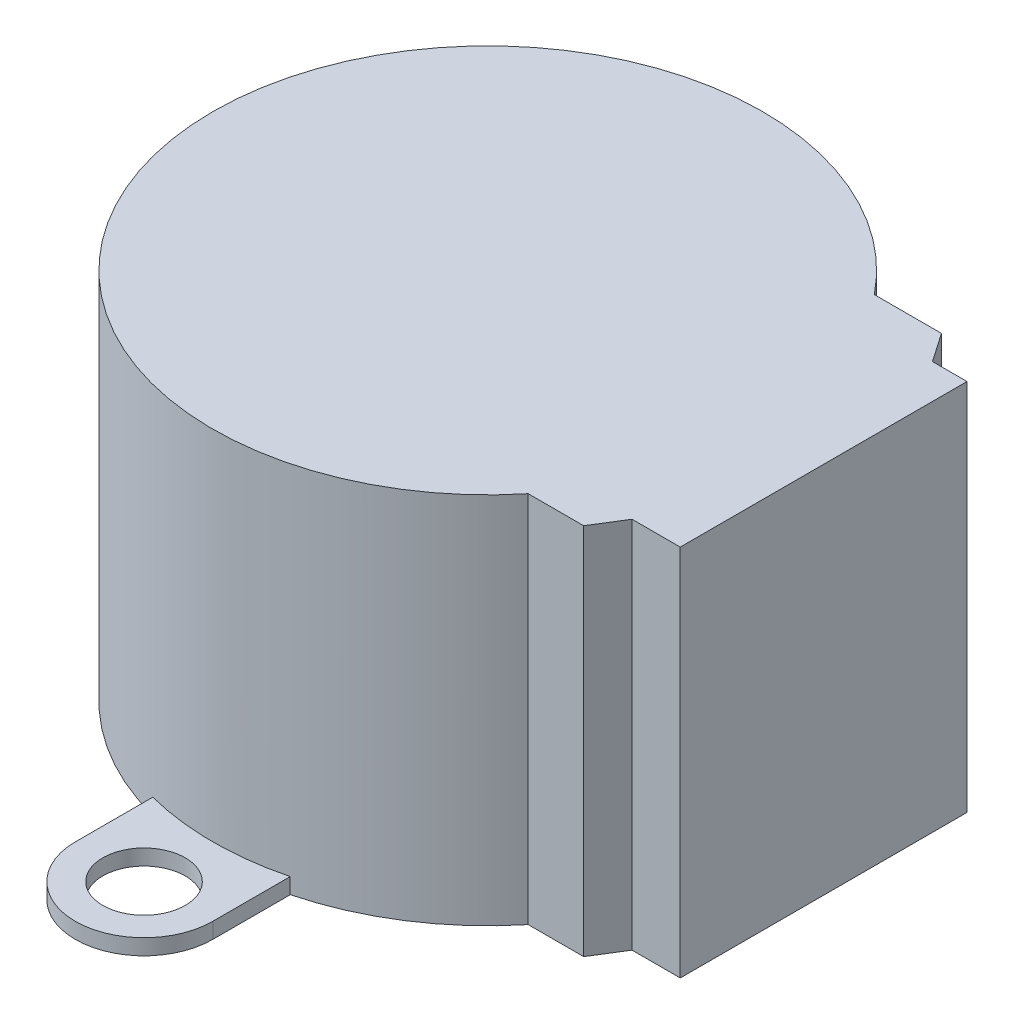
SolidWorks part; units mm, degrees
ref_plane "Front Plane" through (0, 0, 0) normal (0, 0, 1) x (1, 0, 0)
ref_plane "Top Plane" through (0, 0, 0) normal (0, 1, 0) x (1, 0, 0)
ref_plane "Right Plane" through (0, 0, 0) normal (1, 0, 0) x (0, 0, -1)
sketch "Sketch1" plane through (0, 0, 0) normal (0, 1, 0) x (1, 0, 0)
  line L0 (14.3268, 8.7713) -> (15.3419, 7.3)
  line L1 (0, 17.5) -> (0, -17.5) construction
  line L2 (-3.5, 17.5) -> (-3.5, 13.5554)
  line L3 (3.5, 17.5) -> (3.5, 13.5554)
  line L4 (17.1, 7.3) -> (17.1, -7.3)
  line L5 (-3.5, -17.5) -> (-3.5, -13.5554)
  line L6 (3.5, -17.5) -> (3.5, -13.5554)
  line L7 (10.9117, 8.7713) -> (14.3268, 8.7713)
  line L9 (10.8743, -8.8176) -> (13.7006, -8.8176)
  line L13 (13.7006, -8.8176) -> (14.6451, -7.3)
  line L19 (15.3419, 7.3) -> (17.1, 7.3)
  line L22 (14.6451, -7.3) -> (17.1, -7.3)
  circle A0 centre (-8.75, 0) radius 5.25 construction
  arc A1 (10.9117, 8.7713) -> (10.8743, -8.8176) centre (0, 0) ccw
  circle A3 centre (-8, 0) radius 4.5
  circle A4 centre (-8, 0) radius 2.5
  circle A5 centre (0, 17.5) radius 2.1
  circle A6 centre (0, -17.5) radius 2.1
  arc A8 (-3.5, -17.5) -> (3.5, -17.5) centre (0, -17.5) ccw
  arc A9 (3.5, 17.5) -> (-3.5, 17.5) centre (0, 17.5) ccw
  point P19 (17.1, 0)
  point P24 (-12.5, 0)
  point P29 (-14, 0)
  dimension "D1" = 35
  dimension "D2" = 14.6
  dimension "D5" = 4.2
  dimension "D6" = 3.5
  dimension "D8" = 9
  dimension "D9" = 5
  dimension "D10" = 14
  dimension "D3" = 17.5889
  dimension "D4" = 17.1
  dimension "D7" = 8
extrude "Boss-Extrude1" add sketch "Sketch1" along normal blind 19 contours A1 L9 L13 L22 L4 L19 L0 L7 A3 | A4 | A3 A4 region at (2.3709, 0, -0.0105) region at (-12.3727, 0, 0) region at (-8, 0, 0)
extrude "Boss-Extrude2" add sketch "Sketch1<3>" against normal blind 1.6 contours A3 A4 region at (-12.3727, 0, 0)
sketch "Sketch1<3>" plane through (0, 0, 0) normal (0, 1, 0) x (1, 0, 0) same geometry as "Sketch1"
extrude "Boss-Extrude3" add sketch "Sketch1<4>" along normal blind 0.8 contours L3 A9 L2 A1 A5 | L5 A8 L6 A1 A6 region at (0, 0, -14.1022) region at (0, 0, 14.1022)
sketch "Sketch1<4>" plane through (0, 0, 0) normal (0, 1, 0) x (1, 0, 0) same geometry as "Sketch1"
extrude "Boss-Extrude4" add sketch "Sketch1<5>" against normal blind 4 contours A4 region at (-8, 0, 0)
sketch "Sketch1<5>" plane through (0, 0, 0) normal (0, 1, 0) x (1, 0, 0) same geometry as "Sketch1"
sketch "Sketch5" plane through (0, -4, 0) normal (0, -1, 0) x (1, 0, 0)
  line L0 (-10.1451, 1.2839) -> (-5.8549, 1.2839)
  line L1 (-10.1451, -1.2839) -> (-5.8549, -1.2839)
  line L2 (-9.9683, 1.2839) -> (-9.9683, -1.2839) construction
  circle A1 centre (-8, 0) radius 2.5
  circle A2 centre (-8, 0) radius 2.5
  point P9 (-9.9683, 0)
  circle M2 centre (-8, 0) radius 2.5
  dimension "D1" = 0
extrude "Boss-Extrude5" add sketch "Sketch5" along normal blind 6 contours L2 L0 L1 M2 | L0 L2 L1 M2 region at (-10.1899, -4, 0) region at (-7.7902, -4, 0)
fillet "Fillet1" radius 1 1 edges
fillet "Fillet2" radius 1 1 edges
